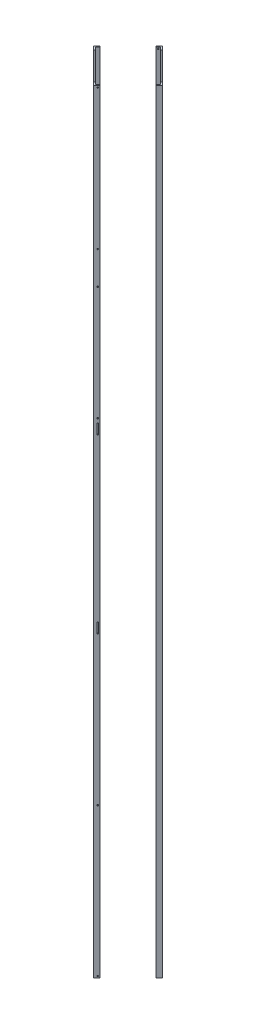
SolidWorks part; units mm, degrees
material "6061-T6 (SS)"
ref_plane "Front Plane" through (0, 0, 0) normal (0, 0, 1) x (1, 0, 0)
ref_plane "Top Plane" through (0, 0, 0) normal (0, 1, 0) x (1, 0, 0)
ref_plane "Right Plane" through (0, 0, 0) normal (1, 0, 0) x (0, 0, -1)
sketch "Sketch2" plane through (0, 0, 0) normal (0, 1, 0) x (1, 0, 0)
  line L0 (0, 94.7743) -> (-8.9803, 85.794)
  line L1 (-8.9803, 85.794) -> (-6.7352, 83.549)
  line L2 (-6.7352, 83.549) -> (0, 90.2842)
  line L3 (0, 90.2842) -> (6.7352, 83.549)
  line L4 (6.7352, 83.549) -> (8.9803, 85.794)
  line L5 (8.9803, 85.794) -> (0, 94.7743)
  line L6 (0, 0) -> (0, 186.644) construction
  line L7 (94.7417, 0.0326) -> (85.7614, 9.0128)
  line L8 (85.7614, 9.0128) -> (83.5164, 6.7678)
  line L9 (83.5164, 6.7678) -> (90.2516, 0.0326)
  line L10 (90.2516, 0.0326) -> (83.5164, -6.7026)
  line L11 (83.5164, -6.7026) -> (85.7614, -8.9477)
  line L12 (85.7614, -8.9477) -> (94.7417, 0.0326)
  line L13 (0, -94.7091) -> (8.9803, -85.7289)
  line L14 (8.9803, -85.7289) -> (6.7352, -83.4838)
  line L15 (6.7352, -83.4838) -> (0, -90.219)
  line L16 (0, -90.219) -> (-6.7352, -83.4838)
  line L17 (-6.7352, -83.4838) -> (-8.9803, -85.7289)
  line L18 (-8.9803, -85.7289) -> (0, -94.7091)
  line L19 (-94.7417, 0.0326) -> (-85.7614, -8.9477)
  line L20 (-85.7614, -8.9477) -> (-83.5164, -6.7026)
  line L21 (-83.5164, -6.7026) -> (-90.2516, 0.0326)
  line L22 (-90.2516, 0.0326) -> (-83.5164, 6.7678)
  line L23 (-83.5164, 6.7678) -> (-85.7614, 9.0128)
  line L24 (-85.7614, 9.0128) -> (-94.7417, 0.0326)
  point P1 (-3.3676, 86.9166)
  point P31 (0, 0.0326)
  dimension "D1" = 127.635
  dimension "D2" = 12.7
  dimension "D3" = 12.7
  dimension "D4" = 3.175
  dimension "D5" = 3.175
  dimension "D7" = 127.635
  dimension "D6" = 4
extrude "Boss-Extrude1" add sketch "Sketch2" along normal blind 2133.6
sketch "Sketch3" plane through (0, 0, 0) normal (0, -1, 0) x (1, 0, 0)
  circle A0 centre (0, 0) radius 94.7417
sketch "Sketch4" plane through (-47.3546, 0, 47.3546) normal (-0.7071, 0, 0.7071) x (0.7071, 0, 0.7071)
  line L0 (-54.3155, 0) -> (-54.3155, 4.7625)
  line L1 (-54.3155, 2133.6) -> (-54.3155, 0) construction
  line L2 (-54.3155, 4.7625) -> (-67.0155, 4.7625)
  line L3 (-67.0155, 2133.6) -> (-67.0155, 0) construction
  line L4 (-67.0155, 0) -> (-54.3155, 0) construction
  circle A0 centre (-59.078, 4.7625) radius 1.7526
  dimension "D2" = 3.5052
  dimension "D3" = 7.9375
  dimension "D4" = 4.7625
  dimension "D1" = 4.7625
extrude "Cut-Extrude1" cut sketch "Sketch4" against normal up to next (3.175 mm away) contours L2 A0 | L2 A0 region at (-89.129, 4.0187, 5.5801) region at (-89.129, 5.5063, 5.5801)
sketch "Sketch5" plane through (-47.3871, 0, -47.3871) normal (-0.7071, 0, -0.7071) x (-0.7071, 0, 0.7071)
  line L0 (-54.3155, 2133.6) -> (-54.3155, 0) construction
  line L1 (-67.0155, 0) -> (-54.3155, 0)
  line L2 (-67.0155, 0) -> (-67.0155, 4.7625)
  line L3 (-67.0155, 4.7625) -> (-54.3155, 4.7625)
  line L4 (-54.3155, 0) -> (-54.3155, 4.7625)
  line L5 (-67.0155, 2133.6) -> (-67.0155, 0) construction
  circle A0 centre (-59.078, 4.7625) radius 1.7526
  dimension "D2" = 3.5052
  dimension "D4" = 4.7625
  dimension "D1" = 4.7625
  dimension "D3" = 7.9375
extrude "Cut-Extrude2" cut sketch "Sketch5" against normal up to next (3.175 mm away) contours L3 A0 | L3 A0 region at (-5.6127, 5.5063, -89.1616) region at (-5.6127, 4.0187, -89.1616)
sketch "Sketch6" plane through (47.3871, 0, -47.3871) normal (0.7071, 0, -0.7071) x (-0.7071, 0, -0.7071)
  line L0 (-54.2695, 2133.6) -> (-54.2695, 0) construction
  line L1 (-66.9695, 0) -> (-54.2695, 0)
  line L2 (-66.9695, 0) -> (-66.9695, 4.7625)
  line L3 (-66.9695, 4.7625) -> (-54.2695, 4.7625)
  line L4 (-54.2695, 0) -> (-54.2695, 4.7625)
  line L5 (-66.9695, 2133.6) -> (-66.9695, 0) construction
  circle A0 centre (-59.032, 4.7625) radius 1.7526
  dimension "D2" = 3.5052
  dimension "D4" = 4.7625
  dimension "D1" = 4.7625
  dimension "D3" = 7.9375
extrude "Cut-Extrude3" cut sketch "Sketch6" against normal up to next (3.175 mm away) contours L3 A0 | L3 A0 region at (89.129, 5.5063, -5.6452) region at (89.129, 4.0187, -5.6452)
sketch "Sketch7" plane through (47.3546, 0, 47.3546) normal (0.7071, 0, 0.7071) x (0.7071, 0, -0.7071)
  line L0 (-54.2695, 2133.6) -> (-54.2695, 0) construction
  line L1 (-66.9695, 0) -> (-54.2695, 0)
  line L2 (-66.9695, 0) -> (-66.9695, 4.7625)
  line L3 (-66.9695, 4.7625) -> (-54.2695, 4.7625)
  line L4 (-54.2695, 0) -> (-54.2695, 4.7625)
  line L5 (-66.9695, 2133.6) -> (-66.9695, 0) construction
  circle A0 centre (-59.032, 4.7625) radius 1.7526
  dimension "D2" = 3.5052
  dimension "D3" = 7.9375
  dimension "D4" = 4.7625
  dimension "D1" = 4.7625
extrude "Cut-Extrude4" cut sketch "Sketch7" against normal up to next (3.175 mm away) contours L3 A0 | L3 A0 region at (5.6127, 5.5063, 89.0965) region at (5.6127, 4.0187, 89.0965)
pattern_linear "LPattern1" count 2 spacing 408.305 along (0, 1, 0) of "Cut-Extrude4", "Cut-Extrude3", "Cut-Extrude1", "Cut-Extrude2"
pattern_linear "LPattern2" count 2 spacing 831.85 along (0, 1, 0) of "Cut-Extrude1", "Cut-Extrude2", "Cut-Extrude3", "Cut-Extrude4"
sketch "Sketch8" plane through (47.3546, 0, 47.3546) normal (0.7071, 0, 0.7071) x (0.7071, 0, -0.7071)
  line L1 (-60.7846, 823.9125) -> (-57.2794, 823.9125)
  line L2 (-60.7846, 823.9125) -> (-60.7846, 849.3125)
  line L3 (-60.7846, 849.3125) -> (-57.2794, 849.3125)
  line L4 (-57.2794, 823.9125) -> (-57.2794, 849.3125)
  line L5 (-60.7846, 823.9125) -> (-57.2794, 849.3125) construction
  line L6 (-60.7846, 849.3125) -> (-57.2794, 823.9125) construction
  arc A0 (-60.7846, 849.3125) -> (-57.2794, 849.3125) centre (-59.032, 849.3125) cw
  arc A1 (-57.2794, 823.9125) -> (-60.7846, 823.9125) centre (-59.032, 823.9125) cw
  point P0 (-59.032, 836.6125)
  circle M5 centre (-59.032, 836.6125) radius 1.7526
  dimension "D1" = 3.5052
  dimension "D2" = 25.4
extrude "Cut-Extrude5" cut sketch "Sketch8" against normal up to next (3.175 mm away) contours A0 L3 | L4 L3 L2 M5 | L1 L4 L2 M5 | A1 L1 region at (5.6127, 829.581, 89.0965) region at (5.6127, 823.1687, 89.0965) region at (5.6127, 843.644, 89.0965) region at (5.6127, 850.0563, 89.0965)
sketch "Sketch9" plane through (-47.3546, 0, 47.3546) normal (-0.7071, 0, 0.7071) x (0.7071, 0, 0.7071)
  line L1 (-60.8306, 823.9125) -> (-57.3254, 823.9125)
  line L2 (-60.8306, 823.9125) -> (-60.8306, 849.3125)
  line L3 (-60.8306, 849.3125) -> (-57.3254, 849.3125)
  line L4 (-57.3254, 823.9125) -> (-57.3254, 849.3125)
  line L5 (-60.8306, 823.9125) -> (-57.3254, 849.3125) construction
  line L6 (-60.8306, 849.3125) -> (-57.3254, 823.9125) construction
  arc A0 (-60.8306, 849.3125) -> (-57.3254, 849.3125) centre (-59.078, 849.3125) cw
  arc A1 (-57.3254, 823.9125) -> (-60.8306, 823.9125) centre (-59.078, 823.9125) cw
  point P0 (-59.078, 836.6125)
  circle M5 centre (-59.078, 836.6125) radius 1.7526
  dimension "D1" = 3.5052
  dimension "D2" = 25.4
extrude "Cut-Extrude6" cut sketch "Sketch9" against normal up to next (3.175 mm away) contours A0 L3 | L4 L3 L2 M5 | L1 L4 L2 M5 | A1 L1 region at (-89.129, 829.581, 5.5801) region at (-89.129, 823.1687, 5.5801) region at (-89.129, 843.644, 5.5801) region at (-89.129, 850.0563, 5.5801)
sketch "Sketch10" plane through (-47.3871, 0, -47.3871) normal (-0.7071, 0, -0.7071) x (-0.7071, 0, 0.7071)
  line L1 (-60.8306, 823.9125) -> (-57.3254, 823.9125)
  line L2 (-60.8306, 823.9125) -> (-60.8306, 849.3125)
  line L3 (-60.8306, 849.3125) -> (-57.3254, 849.3125)
  line L4 (-57.3254, 823.9125) -> (-57.3254, 849.3125)
  line L5 (-60.8306, 823.9125) -> (-57.3254, 849.3125) construction
  line L6 (-60.8306, 849.3125) -> (-57.3254, 823.9125) construction
  arc A0 (-60.8306, 849.3125) -> (-57.3254, 849.3125) centre (-59.078, 849.3125) cw
  arc A1 (-60.8306, 823.9125) -> (-57.3254, 823.9125) centre (-59.078, 823.9125) ccw
  point P0 (-59.078, 836.6125)
  circle M5 centre (-59.078, 836.6125) radius 1.7526
  dimension "D1" = 3.5052
  dimension "D2" = 25.4
extrude "Cut-Extrude7" cut sketch "Sketch10" against normal up to next (3.175 mm away) contours A0 L3 | L4 L3 L2 M5 | L1 L4 L2 M5 | L1 A1 region at (-5.6127, 829.581, -89.1616) region at (-5.6127, 823.1687, -89.1616) region at (-5.6127, 843.644, -89.1616) region at (-5.6127, 850.0563, -89.1616)
sketch "Sketch11" plane through (47.3871, 0, -47.3871) normal (0.7071, 0, -0.7071) x (-0.7071, 0, -0.7071)
  line L1 (-60.7846, 823.9125) -> (-57.2794, 823.9125)
  line L2 (-60.7846, 823.9125) -> (-60.7846, 849.3125)
  line L3 (-60.7846, 849.3125) -> (-57.2794, 849.3125)
  line L4 (-57.2794, 823.9125) -> (-57.2794, 849.3125)
  line L5 (-60.7846, 823.9125) -> (-57.2794, 849.3125) construction
  line L6 (-60.7846, 849.3125) -> (-57.2794, 823.9125) construction
  arc A0 (-60.7846, 849.3125) -> (-57.2794, 849.3125) centre (-59.032, 849.3125) cw
  arc A1 (-60.7846, 823.9125) -> (-57.2794, 823.9125) centre (-59.032, 823.9125) ccw
  point P0 (-59.032, 836.6125)
  circle M5 centre (-59.032, 836.6125) radius 1.7526
  dimension "D1" = 3.5052
  dimension "D2" = 25.4
extrude "Cut-Extrude8" cut sketch "Sketch11" against normal up to next (3.175 mm away) contours A0 L3 | L4 L3 L2 M5 | L1 L4 L2 M5 | L1 A1 region at (89.129, 829.581, -5.6452) region at (89.129, 823.1687, -5.6452) region at (89.129, 843.644, -5.6452) region at (89.129, 850.0563, -5.6452)
pattern_linear "LPattern12" count 2 spacing 1308.1 along (0, 1, 0) of "Cut-Extrude1", "Cut-Extrude2", "Cut-Extrude3", "Cut-Extrude4"
pattern_linear "LPattern13" count 2 spacing 476.25 along (0, 1, 0) of "Cut-Extrude5", "Cut-Extrude6", "Cut-Extrude7", "Cut-Extrude8"
pattern_linear "LPattern16" count 2 spacing 1647.825 along (0, 1, 0) of "Cut-Extrude1", "Cut-Extrude2", "Cut-Extrude3", "Cut-Extrude4"
pattern_linear "LPattern17" count 2 spacing 1333.5 along (0, 1, 0) of "Cut-Extrude1", "Cut-Extrude2", "Cut-Extrude3", "Cut-Extrude4"
pattern_linear "LPattern18" count 2 spacing 1737.995 along (0, 1, 0) of "Cut-Extrude1", "Cut-Extrude2", "Cut-Extrude3", "Cut-Extrude4"
pattern_linear "LPattern19" count 2 spacing 2124.075 along (0, 1, 0) of "Cut-Extrude1", "Cut-Extrude2", "Cut-Extrude3", "Cut-Extrude4"
